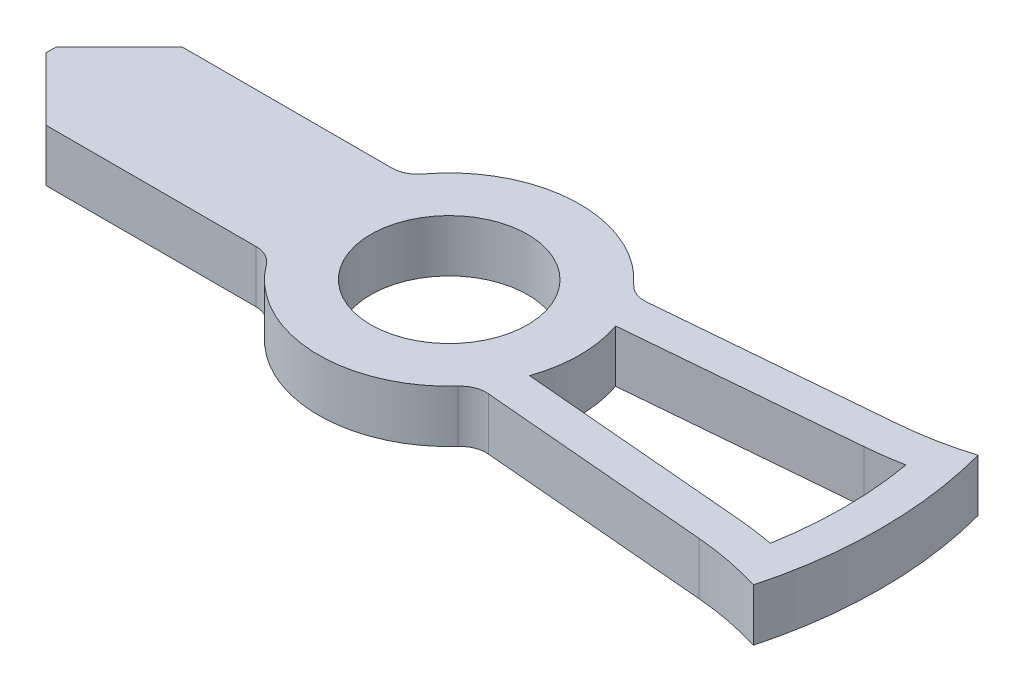
SolidWorks part; units mm, degrees
ref_plane "Front Plane" through (0, 0, 0) normal (0, 0, 1) x (1, 0, 0)
ref_plane "Top Plane" through (0, 0, 0) normal (0, 1, 0) x (1, 0, 0)
ref_plane "Right Plane" through (0, 0, 0) normal (1, 0, 0) x (0, 0, -1)
other "Center of Mass"
sketch "Sketch1" plane through (0, 0, 0) normal (0, 1, 0) x (1, 0, 0)
  line L0 (-82.55, 0) -> (82.55, 0) construction
  line L1 (0, -82.55) -> (0, 15) construction
  line L10 (0, 25) -> (0, 82.55) construction
  line L20 (67.3674, 12.0078) -> (23.606, 8.2315)
  line L24 (66.7655, 18.9819) -> (20.0377, 14.9496)
  line L32 (74.4265, 12.9808) -> (74.4265, 12.9808)
  line L33 (-27.2494, 6.8) -> (-63.2494, 6.8) construction
  line L34 (67.3674, -12.0078) -> (23.606, -8.2315)
  line L35 (-66.2494, 3.8) -> (-66.2494, -3.8) construction
  line L36 (-27.1984, -6.8) -> (-63.2494, -6.8) construction
  line L37 (-27.1984, -6.8) -> (-16.6661, -6.8) construction
  line L38 (-27.2494, 6.8) -> (-16.6661, 6.8) construction
  line L39 (67.609, -12.0287) -> (16.3158, -7.6024) construction
  line L40 (67.3674, 12.0078) -> (16.3158, 7.6024) construction
  line L41 (67.0072, -19.0027) -> (20.0377, -14.9496) construction
  line L42 (74.4306, -12.957) -> (74.4306, -12.957) construction
  line L43 (83.0766, -22.5452) -> (79.7448, -21.3371) construction
  line L44 (66.7655, -18.9819) -> (20.0377, -14.9496)
  line L45 (82.8349, 22.5244) -> (79.7448, 21.3371) construction
  line L46 (-27.2494, 13.8) -> (-63.2494, 13.8) construction
  line L47 (-27.2494, 13.8) -> (-20.8461, 13.8) construction
  line L48 (-27.1984, -13.8) -> (-63.2494, -13.8) construction
  line L49 (-27.1984, -13.8) -> (-20.8461, -13.8) construction
  line L50 (-76.1542, -13) -> (-76.1542, 13)
  line L51 (-76.1542, 13) -> (-21.3542, 13)
  line L52 (-76.1542, -13) -> (-21.3542, -13)
  line L53 (-73.2494, 3.8) -> (-73.2494, -3.8) construction
  circle A0 centre (0, 0) radius 82.55 construction
  circle A6 centre (0, 0) radius 0.0381
  arc A26 (79.706, 21.4815) -> (66.7655, 18.9819) centre (61.3462, 81.7827) cw
  arc A40 (74.4265, -12.9808) -> (74.4265, 12.9808) centre (0, 0) ccw
  arc A41 (74.4265, 12.9808) -> (67.3674, 12.0078) centre (61.3462, 81.7827) cw
  arc A42 (-63.2494, 6.8) -> (-66.2494, 3.8) centre (-63.2494, 3.8) ccw construction
  arc A43 (-63.2494, -6.8) -> (-66.2494, -3.8) centre (-63.2494, -3.8) cw construction
  arc A44 (16.3158, 7.6024) -> (-16.6661, 6.8) centre (0, 0) ccw construction
  arc A46 (-16.6661, -6.8) -> (16.3158, -7.6024) centre (0, 0) ccw construction
  arc A48 (74.4306, -12.957) -> (67.609, -12.0287) centre (61.5879, -81.8035) ccw construction
  arc A49 (79.706, -21.4815) -> (66.7655, -18.9819) centre (61.3462, -81.7827) ccw
  arc A50 (74.4306, -12.957) -> (74.4265, 12.9808) centre (0, 0) ccw construction
  arc A51 (79.7448, -21.3371) -> (79.7448, 21.3371) centre (0, 0) ccw construction
  arc A52 (83.0766, -22.5452) -> (67.0072, -19.0027) centre (61.5879, -81.8035) ccw construction
  arc A53 (74.4265, -12.9808) -> (67.3674, -12.0078) centre (61.3462, -81.7827) ccw
  arc A55 (82.8349, 22.5244) -> (66.7655, 18.9819) centre (61.3462, 81.7827) cw construction
  arc A56 (79.706, -21.4815) -> (79.706, 21.4815) centre (0, 0) ccw
  arc A57 (-63.2494, 13.8) -> (-73.2494, 3.8) centre (-63.2494, 3.8) ccw construction
  arc A58 (-63.2494, -13.8) -> (-73.2494, -3.8) centre (-63.2494, -3.8) cw construction
  arc A59 (20.0377, 14.9496) -> (-21.3542, 13) centre (0, 0) ccw
  arc A60 (20.0377, 14.9496) -> (-20.8461, 13.8) centre (0, 0) ccw construction
  arc A61 (-20.8461, -13.8) -> (20.0377, -14.9496) centre (0, 0) ccw construction
  arc A62 (23.606, -8.2315) -> (23.606, 8.2315) centre (0, 0) ccw
  arc A63 (-21.3542, -13) -> (20.0377, -14.9496) centre (0, 0) ccw
  point P6 (0, 0)
  point P10 (0, 0)
  point P11 (-20.2018, 14.7271)
  point P12 (14.4373, 20.4099)
  point P13 (78.3727, 25.9271)
  point P14 (-51.1, 37.2518)
  point P16 (-51.1, -37.2518)
  point P17 (14.4373, -20.4099)
  point P18 (78.3727, -25.9271)
  point P19 (73.26, -18.4599)
  point P20 (73.26, 18.4599)
  point P21 (12.2435, 13.1946)
  point P22 (0, 0)
  point P23 (-17.5239, 4.1123)
  point P24 (-49.2137, 27.214)
  point P25 (0, 0)
  point P26 (-49.2137, -27.214)
  point P27 (-17.5239, -4.1123)
  point P28 (0, 0)
  point P29 (12.2435, -13.1946)
  point P42 (-76.1542, 0)
  point P60 (0, 0)
  point P66 (0, 0)
  point P83 (-76.1542, 0)
  point P87 (0, 0)
  point P92 (0, 0)
  dimension "D1" = 165.1
  dimension "D2" = 25
  dimension "D5" = 0.0762
  dimension "D4" = 4.932
  dimension "D3" = 7
  dimension "D8" = 63.0342
  dimension "D7" = 54.8
  dimension "D9" = 46.9015
  dimension "D6" = 13
  dimension "D10" = 14.9496
  dimension "D11" = 74.4265
extrude "Boss-Extrude1" add sketch "Sketch1" along normal blind 10 contours A49 A56 A26 L24 L44 A40 A53 L34 L20 A41 A6 region at (-2.3941, 0, 0)
sketch "Sketch3" plane through (0, 10, 0) normal (0, 1, 0) x (1, 0, 0)
  circle A0 centre (0, 0) radius 15
  dimension "D1" = 30
extrude "Cut-Extrude3" cut sketch "Sketch3" against normal blind 10
fillet "Fillet4" radius 5 4 edges at (20.0377, 5, 14.9496) (-21.3542, 5, 13) (-21.3542, 5, -13) (20.0377, 5, -14.9496)
chamfer "Chamfer1" distance 12 angle 45 2 edges at (-76.1542, 5, -13) (-76.1542, 5, 13)
